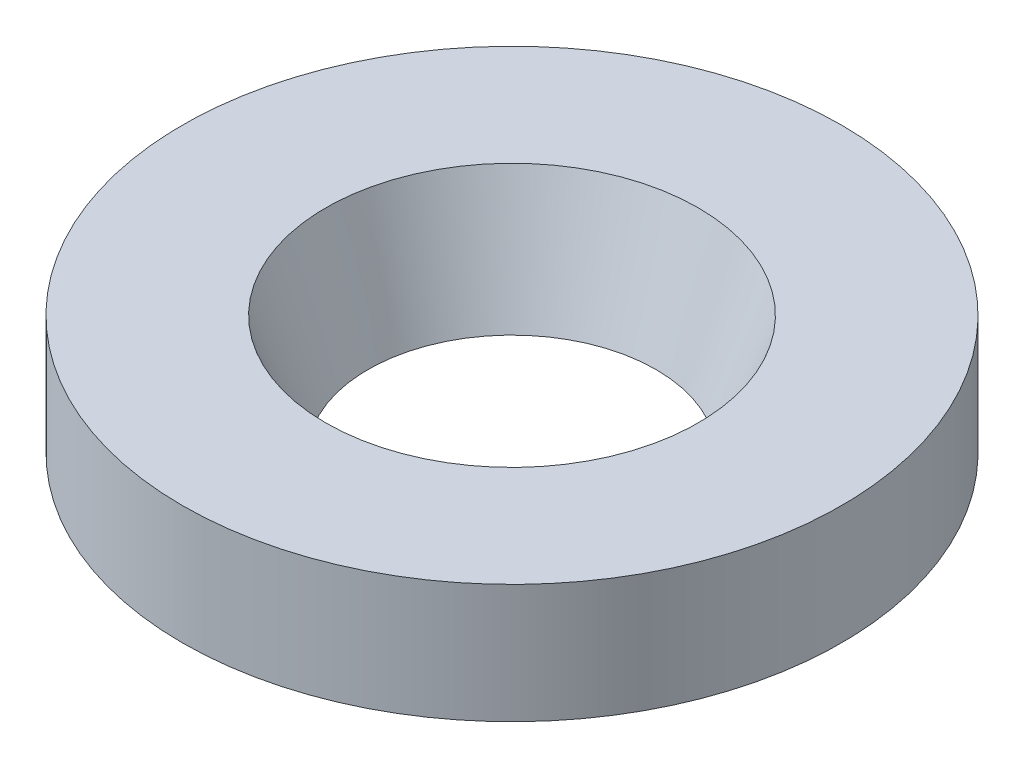
SolidWorks part; units mm, degrees
material "Nylon 101"
ref_plane "Front Plane" through (0, 0, 0) normal (0, 0, 1) x (1, 0, 0)
ref_plane "Top Plane" through (0, 0, 0) normal (0, 1, 0) x (1, 0, 0)
ref_plane "Right Plane" through (0, 0, 0) normal (1, 0, 0) x (0, 0, -1)
sketch "Sketch1" plane through (0, 0, 0) normal (0, 1, 0) x (1, 0, 0)
  circle A0 centre (0, 0) radius 5.842
  circle A1 centre (0, 0) radius 3.302
  dimension "D1" = 6.604
  dimension "D2" = 11.684
extrude "Boss-Extrude1" add sketch "Sketch1" along normal blind 2.1082
sketch "Sketch3" plane through (0, 0, 0) normal (0, 0, 1) x (1, 0, 0)
  line L0 (-3.302, 2.1082) -> (-2.5527, 0)
  line L1 (-2.5527, 0) -> (-3.302, 0)
  line L2 (-3.302, 0) -> (-3.302, 2.1082)
  line L3 (0, 0) -> (0, 2.1082) construction
  dimension "D1" = 2.5527
revolve "Revolve1" add sketch "Sketch3" angle 360 about L3
